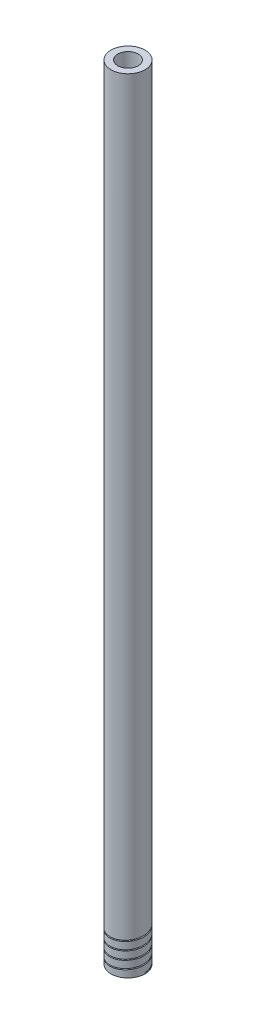
SolidWorks part; units mm, degrees
ref_plane "Front Plane" through (0, 0, 0) normal (0, 0, 1) x (1, 0, 0)
ref_plane "Top Plane" through (0, 0, 0) normal (0, 1, 0) x (1, 0, 0)
ref_plane "Right Plane" through (0, 0, 0) normal (1, 0, 0) x (0, 0, -1)
sketch "Sketch1" plane through (0, 0, 0) normal (0, 1, 0) x (1, 0, 0)
  circle A0 centre (0, 0) radius 25
  dimension "D1" = 50
extrude "Boss-Extrude1" add sketch "Sketch1" along normal blind 100
sketch "Sketch2" plane through (0, 100, 0) normal (0, 1, 0) x (1, 0, 0)
  circle A0 centre (0, 0) radius 25
  dimension "D1" = 50
extrude "Boss-Extrude2" add sketch "Sketch2" along normal blind 1050
thread "Thread1" pitch 2 method cut profile "Thread Profile1" start angle 0, offset 0, length 50, pitch 12, diameter 50
ref_plane "Plane4" through (25, 0, 0) normal (0, 0, 1) x (1, 0, 0)
sketch "Thread Profile1" plane through (25, 0, 0) normal (0, 0, 1) x (1, 0, 0)
  line L0 (0, 0) -> (0, 2) construction
  line L11 (0, 0) -> (0, 1.75)
  line L12 (0, 1.75) -> (-1.0825, 1.125)
  line L13 (-1.0825, 1.125) -> (-1.0825, 0.625)
  line L15 (-1.0825, 0.625) -> (0, 0)
  line L17 (-1.0825, 0.875) -> (0, 0.875) construction
  point P2 (0, 0)
  dimension "Pitch" = 2
  dimension "Profile_Angle" = 60
  dimension "Profile_Land" = 0.5
  dimension "Profile_Height" = 1.0825
sketch "Sketch5" plane through (0, 1150, 0) normal (0, 1, 0) x (1, 0, 0)
  circle A0 centre (0, 0) radius 15
  dimension "D1" = 30
extrude "Cut-Extrude1" cut sketch "Sketch5" against normal blind 75
